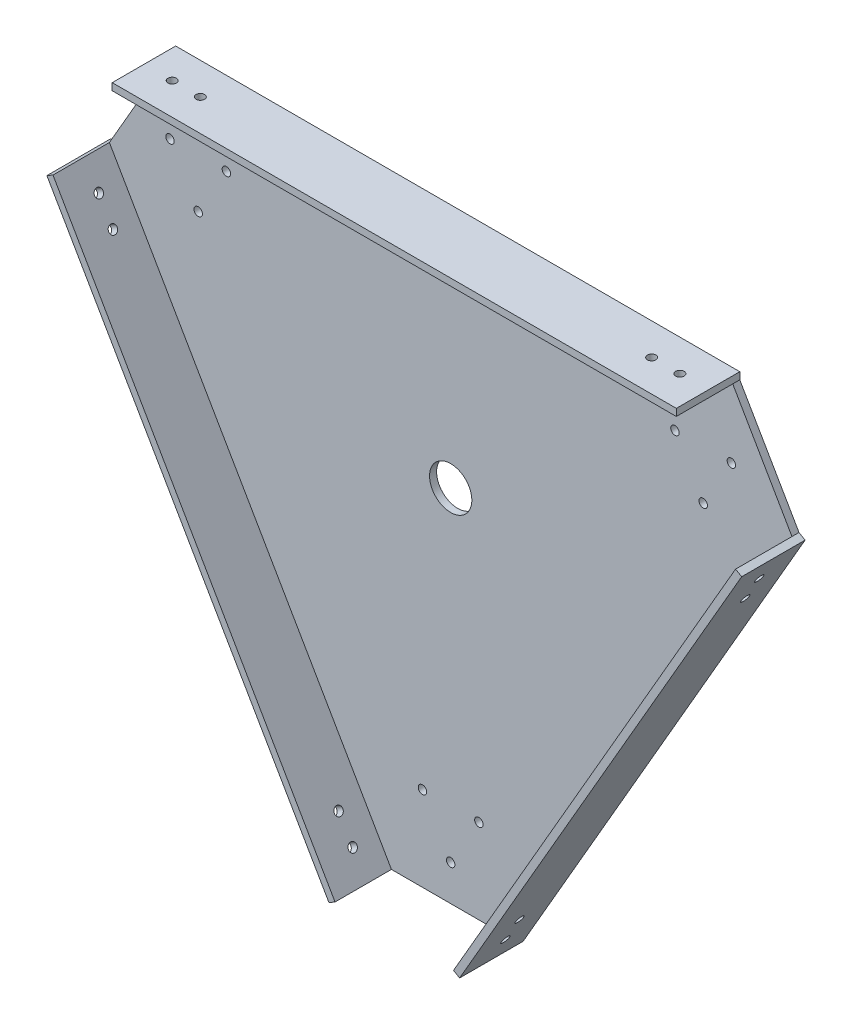
SolidWorks part; units mm, degrees
ref_plane "Спереди" through (0, 0, 0) normal (0, 0, 1) x (1, 0, 0)
ref_plane "Сверху" through (0, 0, 0) normal (0, 1, 0) x (1, 0, 0)
ref_plane "Справа" through (0, 0, 0) normal (1, 0, 0) x (0, 0, -1)
sketch "Эскиз1" plane through (0, 0, 0) normal (0, 0, 1) x (1, 0, 0)
  line L0 (0, 0) -> (21, 36.3731)
  line L1 (21, 36.3731) -> (221, 36.3731)
  line L2 (221, 36.3731) -> (242, 0)
  line L3 (242, 0) -> (142, -173.2051)
  line L4 (142, -173.2051) -> (100, -173.2051)
  line L5 (100, -173.2051) -> (0, 0)
  line L7 (31.4812, -5.474) -> (21.4812, 11.8465) construction
  line L8 (21.4812, 11.8465) -> (41.4812, 11.8465) construction
  line L9 (41.4812, 11.8465) -> (31.4812, -5.474) construction
  line L10 (21.4812, 11.8465) -> (10.5, 18.1865) construction
  line L11 (220.5188, 11.8465) -> (231.5, 18.1865) construction
  line L12 (210.5188, -5.474) -> (200.5188, 11.8465) construction
  line L13 (200.5188, 11.8465) -> (220.5188, 11.8465) construction
  line L14 (220.5188, 11.8465) -> (210.5188, -5.474) construction
  line L15 (121, -160.5251) -> (111, -143.2046) construction
  line L16 (111, -143.2046) -> (131, -143.2046) construction
  line L17 (131, -143.2046) -> (121, -160.5251) construction
  line L18 (121, -160.5251) -> (121, -173.2051) construction
  line L19 (121, -173.2051) -> (121, 36.3731) construction
  line L20 (10.5, 18.1865) -> (192, -86.6025) construction
  circle A0 centre (21.4812, 11.8465) radius 1.5
  circle A1 centre (41.4812, 11.8465) radius 1.5
  circle A2 centre (31.4812, -5.474) radius 1.5
  circle A3 centre (200.5188, 11.8465) radius 1.5
  circle A4 centre (220.5188, 11.8465) radius 1.5
  circle A5 centre (210.5188, -5.474) radius 1.5
  circle A6 centre (111, -143.2046) radius 1.5
  circle A7 centre (131, -143.2046) radius 1.5
  circle A8 centre (121, -160.5251) radius 1.5
  circle A9 centre (121, -45.6107) radius 7.5
  point P27 (121, -45.6107)
  dimension "D5" = 3
  dimension "D8" = 15
  dimension "D1" = 42
  dimension "D2" = 60
  dimension "D3" = 60
  dimension "D4" = 200
  dimension "D6" = 12.68
  dimension "D7" = 20
extrude "Бобышка-Вытянуть1" add sketch "Эскиз1" along normal blind 2.5
sketch "Эскиз2" plane through (0, 0, 0) normal (0, 0, -1) x (-1, 0, 0)
  line L0 (0, 0) -> (2.1651, -1.25)
  line L1 (2.1651, -1.25) -> (-97.8349, -174.4551)
  line L2 (-97.8349, -174.4551) -> (-100, -173.2051)
  line L3 (0, 0) -> (-100, -173.2051) construction
  line L4 (-21, 36.3731) -> (-21, 38.8731)
  line L5 (-21, 38.8731) -> (-221, 38.8731)
  line L6 (-221, 38.8731) -> (-221, 36.3731)
  line L7 (-242, 0) -> (-244.1651, -1.25)
  line L8 (-244.1651, -1.25) -> (-144.1651, -174.4551)
  line L9 (-144.1651, -174.4551) -> (-142, -173.2051)
  line L10 (-142, -173.2051) -> (-242, 0) construction
  line L11 (-221, 36.3731) -> (-21, 36.3731) construction
  line L12 (-242, 0) -> (-142, -173.2051)
  line L13 (-100, -173.2051) -> (0, 0)
  line L14 (-21, 36.3731) -> (-221, 36.3731)
  dimension "D1" = 2.5
extrude "Бобышка-Вытянуть2" add sketch "Эскиз2" against normal blind 22.5
sketch "Эскиз3" plane through (0, 38.8731, 0) normal (0, 1, 0) x (1, 0, 0)
  line L0 (211, -22.5) -> (211, 0) construction
  line L1 (21, -22.5) -> (221, -22.5) construction
  line L2 (21, 0) -> (221, 0) construction
  line L3 (221, -22.5) -> (221, 0) construction
  line L4 (201, -22.5) -> (201, 0) construction
  line L5 (41, -22.5) -> (41, 0) construction
  line L6 (31, -22.5) -> (31, 0) construction
  line L7 (21, -22.5) -> (21, 0) construction
  circle A0 centre (211, -11.25) radius 1.5
  circle A1 centre (201, -11.25) radius 1.5
  circle A2 centre (41, -11.25) radius 1.5
  circle A3 centre (31, -11.25) radius 1.5
  dimension "D1" = 3
  dimension "D2" = 10
  dimension "D5" = 10
  dimension "D7" = 10
  dimension "D3" = 2
  dimension "D4" = 2
  dimension "D6" = 2
extrude "Вырез-Вытянуть1" cut sketch "Эскиз3" against normal up to next
sketch "Эскиз6" plane through (183.6651, -106.0391, 0) normal (0.866, -0.5, 0) x (0, 0, -1)
  line L0 (-22.5, -69) -> (0, -69) construction
  line L1 (-22.5, -59) -> (0, -59) construction
  line L2 (-22.5, 101) -> (0, 101) construction
  line L3 (-22.5, 111) -> (0, 111) construction
  line L4 (0, 121) -> (0, -79) construction
  line L5 (-22.5, 121) -> (-22.5, -79) construction
  line L6 (-22.5, 121) -> (0, 121) construction
  line L7 (-22.5, -79) -> (0, -79) construction
  circle A3 centre (-11.25, 111) radius 1.5
  circle A4 centre (-11.25, 101) radius 1.5
  circle A5 centre (-11.25, -59) radius 1.5
  circle A6 centre (-11.25, -69) radius 1.5
  dimension "D1" = 2
  dimension "D6" = 3
  dimension "D2" = 10
  dimension "D3" = 10
  dimension "D5" = 10
  dimension "D4" = 2
extrude "Вырез-Вытянуть2" cut sketch "Эскиз6" against normal up to next
sketch "Эскиз7" plane through (-2.1651, -1.25, 0) normal (-0.866, -0.5, 0) x (0, 0, 1)
  line L0 (22.5, 0) -> (0, 0) construction
  line L1 (22.5, -200) -> (22.5, 0) construction
  line L2 (0, -20) -> (22.5, -20) construction
  line L3 (0, -10) -> (22.5, -10) construction
  line L4 (0, -200) -> (0, 0) construction
  line L5 (0, -190) -> (22.5, -190) construction
  line L6 (0, -180) -> (22.5, -180) construction
  line L7 (22.5, -200) -> (0, -200) construction
  circle A0 centre (11.25, -10) radius 1.5
  circle A1 centre (11.25, -20) radius 1.5
  circle A4 centre (11.25, -180) radius 1.5
  circle A5 centre (11.25, -190) radius 1.5
  dimension "D2" = 3
  dimension "D1" = 10
  dimension "D3" = 10
  dimension "D5" = 10
  dimension "D4" = 2
extrude "Вырез-Вытянуть3" cut sketch "Эскиз7" against normal up to next
sketch "Эскиз8" plane through (181.5, 104.7891, 0) normal (0.866, 0.5, 0) x (0, 0, -1)
